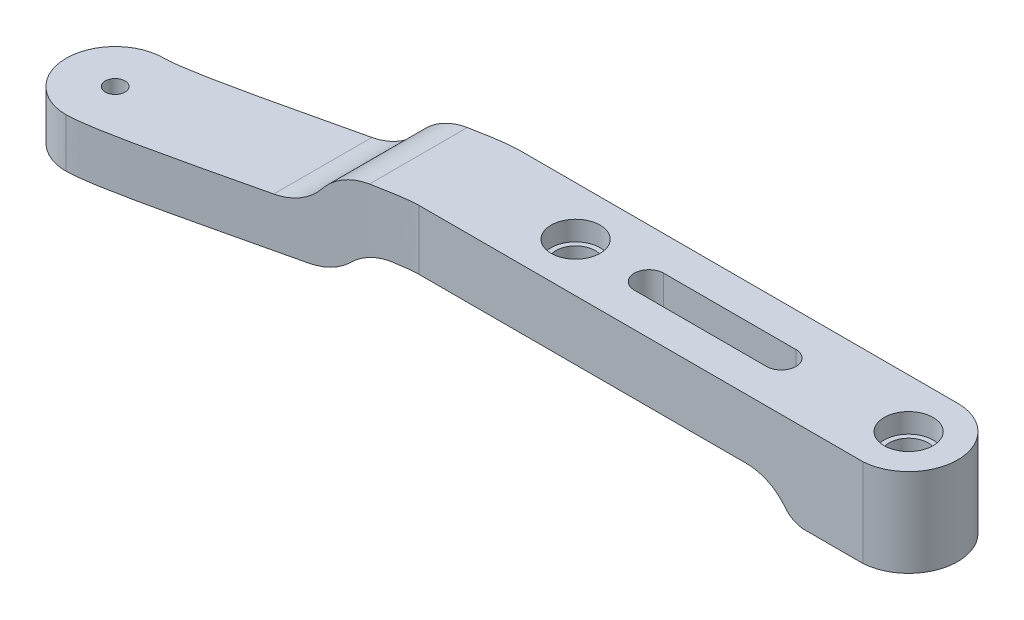
SolidWorks part; units mm, degrees
ref_plane "Front Plane" through (0, 0, 0) normal (0, 0, 1) x (1, 0, 0)
ref_plane "Top Plane" through (0, 0, 0) normal (0, 1, 0) x (1, 0, 0)
ref_plane "Right Plane" through (0, 0, 0) normal (1, 0, 0) x (0, 0, -1)
sketch "Sketch1" plane through (0, 0, 0) normal (0, 1, 0) x (1, 0, 0)
  line L0 (-99.7903, -9.9902) -> (-120.5978, -9.9902) construction
  line L1 (-89.6393, 10.0098) -> (0.3607, 10.0098)
  line L3 (-90, -9.9902) -> (0.7215, -9.9902)
  line L5 (-89.6393, 10.0098) -> (0, 0) construction
  line L6 (-90, -9.9902) -> (0, 0) construction
  line L7 (-142.7139, -21.9902) -> (-157.2861, -21.9902) construction
  line L8 (-139.5582, -1.9902) -> (-160.4418, -1.9902) construction
  line L9 (-103.3936, 10.0098) -> (-117.8223, 10.0098) construction
  line L18 (-44.6393, 10.0098) -> (-44.6393, -9.9902) construction
  arc A4 (0.7215, -9.9902) -> (0.3607, 10.0098) centre (0, 0) ccw
  arc A5 (-150, -1.9902) -> (-150, -21.9902) centre (-150, -11.9902) ccw
  spline S0 degree 3 poles (-150, -1.9902) (-141.2985, -1.9902) (-98.6572, 10.0098) (-89.6393, 10.0098) knots 0 0 0 0 1 1 1 1
  spline S1 degree 3 poles (-150, -21.9902) (-140.8924, -21.9902) (-98.6698, -9.9902) (-90, -9.9902) knots 0 0 0 0 1 1 1 1
  point P0 (0, 0)
  dimension "D3" = 12
  dimension "D4" = 12
  dimension "D2" = 90
  dimension "D5" = 150
  dimension "D1" = 20
  dimension "D6" = 90
extrude "Boss-Extrude1" add sketch "Sketch1" along normal blind 18
sketch "Sketch4" plane through (0, 18, 0) normal (0, 1, 0) x (1, 0, 0)
  line L1 (-90, -9.9902) -> (0.7215, -9.9902) construction
  circle A1 centre (-68, 0.0098) radius 2
  dimension "D1" = 68
  dimension "D3" = 4
  dimension "D4" = 10
extrude "Cut-Extrude2" cut sketch "Sketch4" against normal blind 20
sketch "Sketch10" plane through (0, 18, 0) normal (0, 1, 0) x (1, 0, 0)
  line L0 (-105, -36) -> (-225, -36)
  line L1 (-225, -36) -> (-225, 14)
  line L2 (-225, 14) -> (-105, 14)
  line L3 (-105, 14) -> (-105, -36)
  dimension "D1" = 50
  dimension "D2" = 120
  dimension "D3" = 14
  dimension "D4" = 105
extrude "Cut-Extrude6" cut sketch "Sketch10" against normal blind 8
sketch "Sketch15" plane through (0, 18, 0) normal (0, 1, 0) x (1, 0, 0)
  circle A0 centre (0, 0) radius 4
  dimension "D1" = 8
extrude "Cut-Extrude9" cut sketch "Sketch15" against normal blind 14 contours A0
sketch "Sketch18" plane through (0, 10, 0) normal (0, 1, 0) x (1, 0, 0)
  circle A0 centre (-150, -11.9902) radius 2
  dimension "D1" = 4
extrude "Cut-Extrude12" cut sketch "Sketch18" against normal blind 17
sketch "Sketch22" plane through (0, 0, 0) normal (0, -1, 0) x (1, 0, 0)
  circle A0 centre (0, 0) radius 5
  dimension "D1" = 10
extrude "Cut-Extrude14" cut sketch "Sketch22" against normal blind 4
sketch "Sketch24" plane through (0, 0, -10.0098) normal (0, 0, -1) x (-1, 0, 0)
  line L0 (-0.3607, 0) -> (89.6393, 0) construction
  line L1 (14, 0) -> (104, 0)
  line L2 (14, 0) -> (14, 5.8)
  line L3 (14, 5.8) -> (104, 5.8)
  line L4 (104, 0) -> (104, 5.8)
  line L5 (14, 0) -> (104, 5.8) construction
  line L6 (14, 5.8) -> (104, 0) construction
  point P4 (59, 2.9)
  dimension "D1" = 14
  dimension "D2" = 90
  dimension "D3" = 5.8
extrude "Cut-Extrude16" cut sketch "Sketch24" against normal blind 30
fillet "Fillet13" radius 10 1 edges at (-14, 5.8, -0.0098)
fillet "Fillet14" radius 5 1 edges at (-14, 0, -0.0098)
fillet "Fillet15" radius 10 1 edges at (-104, 5.8, 2.3561)
fillet "Fillet17" radius 10 1 edges at (-104, 0, 2.3561)
fillet "Fillet18" radius 10 1 edges at (-105, 10, 2.5743)
fillet "Fillet19" radius 10 1 edges at (-105, 18, 2.5743)
sketch "Sketch26" plane through (0, 18, 0) normal (0, 1, 0) x (1, 0, 0)
  circle A0 centre (0, 0) radius 5
  dimension "D1" = 10
extrude "Cut-Extrude18" cut sketch "Sketch26" against normal blind 4 contours A0
sketch "Sketch27" plane through (0, 18, 0) normal (0, 1, 0) x (1, 0, 0)
  circle A0 centre (-68, 0.0098) radius 4
  dimension "D1" = 8
extrude "Cut-Extrude19" cut sketch "Sketch27" against normal through all
sketch "Sketch30" plane through (0, 18, 0) normal (0, 1, 0) x (1, 0, 0)
  circle A0 centre (-68, 0.0098) radius 5
  dimension "D1" = 10
extrude "Cut-Extrude22" cut sketch "Sketch30" against normal blind 4
sketch "Sketch31" plane through (0, 5.8, 0) normal (0, -1, 0) x (1, 0, 0)
  circle A0 centre (-68, -0.0098) radius 5
  dimension "D1" = 10
extrude "Cut-Extrude23" cut sketch "Sketch31" against normal blind 4
sketch "Sketch32" plane through (0, 18, 0) normal (0, 1, 0) x (1, 0, 0)
  line L0 (-53, 0) -> (-26, 0) construction
  line L1 (-53, 3) -> (-26, 3)
  line L2 (-53, -3) -> (-26, -3)
  arc A0 (-53, 3) -> (-53, -3) centre (-53, 0) ccw
  arc A1 (-26, -3) -> (-26, 3) centre (-26, 0) ccw
  circle A2 centre (-68, 0.0098) radius 4 construction
  point P3 (-39.5, 0)
  point P8 (-56, 0)
  dimension "D1" = 3
  dimension "D2" = 27
  dimension "D3" = 12
extrude "Cut-Extrude24" cut sketch "Sketch32" against normal through all
